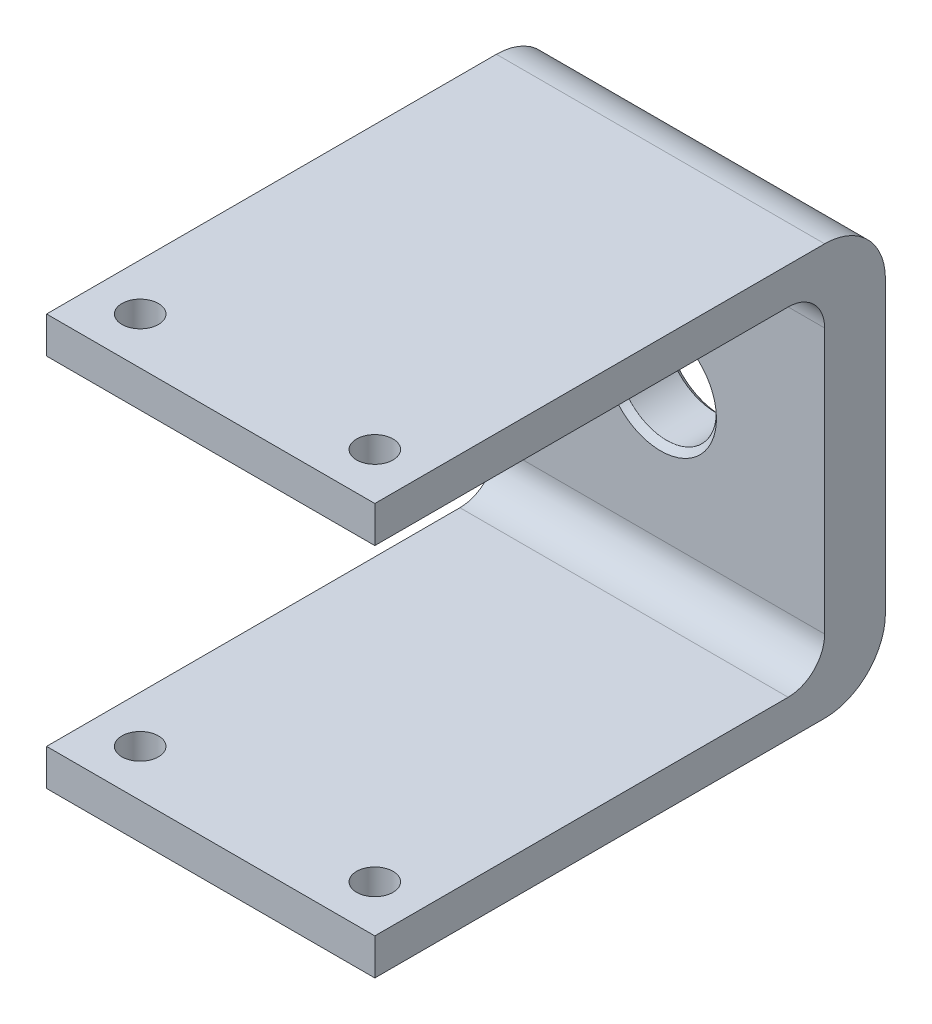
SolidWorks part; units mm, degrees
ref_plane "Front Plane" through (0, 0, 0) normal (0, 0, 1) x (1, 0, 0)
ref_plane "Top Plane" through (0, 0, 0) normal (0, 1, 0) x (1, 0, 0)
ref_plane "Right Plane" through (0, 0, 0) normal (1, 0, 0) x (0, 0, -1)
sketch "Sketch1" plane through (0, 0, 0) normal (0, 1, 0) x (1, 0, 0)
  line L1 (26.3226, -122.1506) -> (53.3226, -122.1506)
  line L6 (39.8226, -117.7121) -> (39.8226, -164.0922) construction
  line L7 (26.3226, -159.1506) -> (53.3226, -159.1506)
  line L8 (26.3226, -159.1506) -> (26.3226, -117.1506)
  line L9 (26.3226, -117.1506) -> (53.3226, -117.1506)
  line L10 (53.3226, -159.1506) -> (53.3226, -117.1506)
  circle A2 centre (49.4726, -155.3006) radius 1.5
  circle A3 centre (30.1726, -155.3006) radius 1.5
  point P18 (39.8226, -159.1506)
  dimension "D1" = 27
  dimension "D2" = 42
  dimension "D3" = 19.3
  dimension "D4" = 3.85
  dimension "D5" = 5
  dimension "D6" = 3.85
extrude "Boss-Extrude1" add sketch "Sketch1" along normal blind 3 contours L6 L1 L8 L7 A3 | L1 L6 L7 L10 A2 | L6 L9 L8 L1 | L9 L6 L1 L10 region at (26.5972, 0, 119.6506) region at (33.1142, 0, 140.4404) region at (46.531, 0, 140.4404)
extrude "Boss-Extrude2" add sketch "Sketch1<3>" against normal blind 13.9 contours L1 L10 L9 L8 region at (39.8226, 0, 119.6506)
sketch "Sketch1<3>" plane through (0, 0, 0) normal (0, 1, 0) x (1, 0, 0) same geometry as "Sketch1"
fillet "Fillet1" radius 3 1 edges at (39.8226, 0, 122.1506)
fillet "Fillet2" radius 5 1 edges at (39.8226, 3, 117.1506)
mirror "Mirror7" about plane through (0, -13.9, 0) normal (0, 1, 0) of bodies 102
sketch "Sketch3" plane through (0, 0, 117.1506) normal (0, 0, -1) x (-1, 0, 0)
  line L0 (-26.3226, -2) -> (-53.3226, -2) construction
  line L1 (-53.3226, -2) -> (-53.3226, -25.8) construction
  circle A0 centre (-39.8226, -13.9) radius 4.1
  point P4 (-39.8226, -2)
  point P7 (-53.3226, -13.9)
extrude "Cut-Extrude1" cut sketch "Sketch3" against normal blind 13.9
fillet "Fillet3" radius 0.5 2 edges at (43.9226, -13.9, 122.1506) (35.7226, -13.9, 117.1506) conic radius 10
